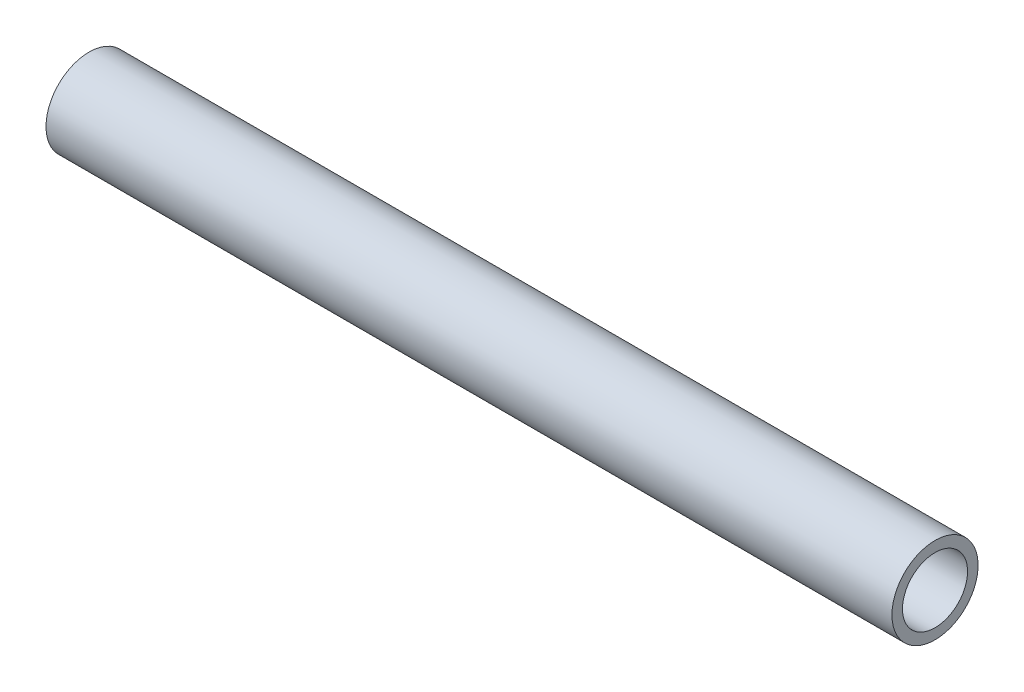
SolidWorks part; units mm, degrees
ref_plane "Front Plane" through (0, 0, 0) normal (0, 0, 1) x (1, 0, 0)
ref_plane "Top Plane" through (0, 0, 0) normal (0, 1, 0) x (1, 0, 0)
ref_plane "Right Plane" through (0, 0, 0) normal (1, 0, 0) x (0, 0, -1)
sketch "Hose_10 Sketch" plane through (0, 0, 0) normal (0, 0, 1) x (1, 0, 0)
  line L0 (-1000, 0) -> (1000, 0) construction
  line L1 (-82.5, 6.35) -> (-82.5, 8.4)
  line L2 (-82.5, 8.4) -> (82.5, 8.4)
  line L3 (82.5, 8.4) -> (82.5, 6.35)
  line L4 (82.5, 6.35) -> (-82.5, 6.35)
revolve "Hose_10" add sketch "Hose_10 Sketch" angle 360 about L0
ref_axis "Engine Axis" through (90.75, 0, 0) along (-1, 0, 0)
